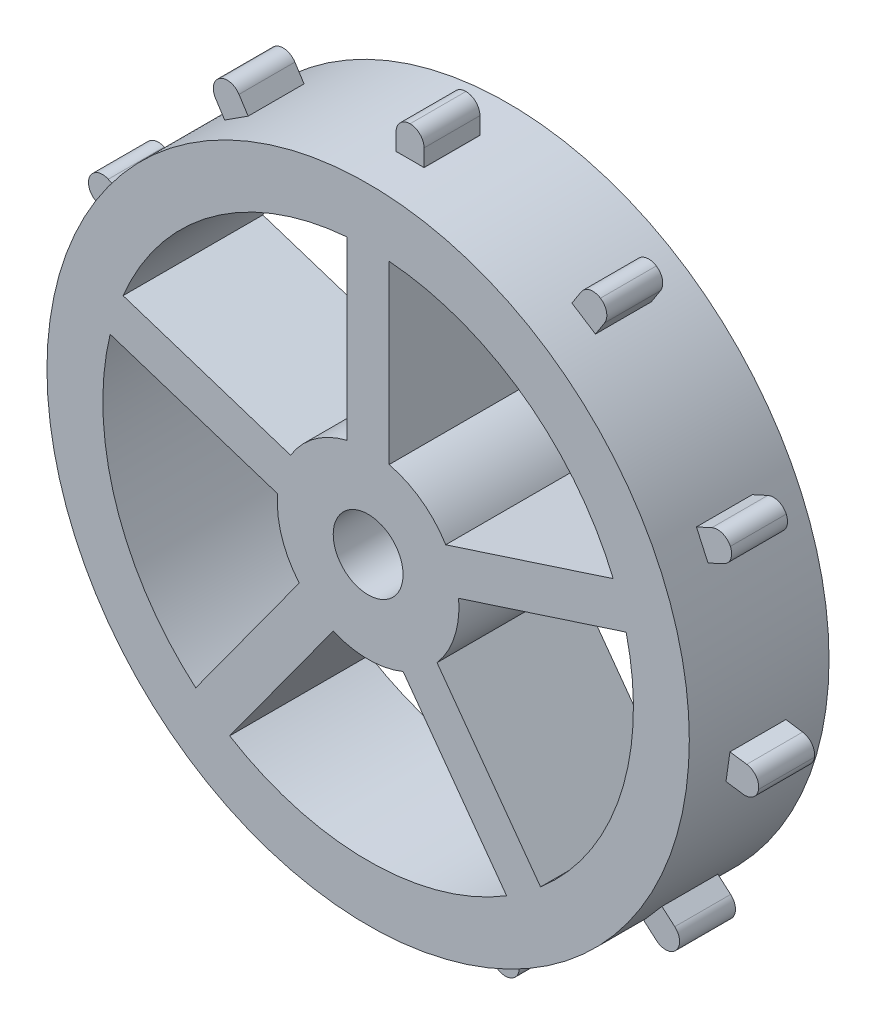
SolidWorks part; units mm, degrees
ref_plane "Front Plane" through (0, 0, 0) normal (0, 0, 1) x (1, 0, 0)
ref_plane "Top Plane" through (0, 0, 0) normal (0, 1, 0) x (1, 0, 0)
ref_plane "Right Plane" through (0, 0, 0) normal (1, 0, 0) x (0, 0, -1)
sketch "Sketch2" plane through (0, 0, 0) normal (0, 0, 1) x (1, 0, 0)
  line L0 (-6.75, 22.9884) -> (6.75, 22.9884)
  line L3 (6.75, 22.9884) -> (18.1069, 15.6897)
  line L4 (18.1069, 15.6897) -> (23.715, 3.4097)
  line L5 (23.715, 3.4097) -> (21.7938, -9.9529)
  line L6 (21.7938, -9.9529) -> (12.9532, -20.1555)
  line L7 (12.9532, -20.1555) -> (0, -23.9589)
  line L8 (0, -23.9589) -> (-12.9532, -20.1555)
  line L9 (-12.9532, -20.1555) -> (-21.7938, -9.9529)
  line L10 (-21.7938, -9.9529) -> (-23.715, 3.4097)
  line L11 (-23.715, 3.4097) -> (-18.1069, 15.6897)
  line L12 (-18.1069, 15.6897) -> (-6.75, 22.9884)
  line L13 (11.5754, 19.8614) -> (12.6567, 21.5439)
  line L14 (-1, 22.9666) -> (1, 22.9666)
  line L15 (-1, 22.9666) -> (-1, 24.9666)
  line L17 (1, 22.9666) -> (1, 24.9666)
  line L18 (13.258, 18.7801) -> (14.3392, 20.4626)
  line L19 (20.4758, 10.4503) -> (22.295, 11.2811)
  line L20 (21.3066, 8.6311) -> (23.1259, 9.4619)
  line L21 (22.8752, -2.2787) -> (24.8548, -2.5633)
  line L22 (22.5905, -4.2583) -> (24.5702, -4.5429)
  line L23 (18.0119, -14.2842) -> (19.5234, -15.5939)
  line L24 (16.7022, -15.7957) -> (18.2137, -17.1054)
  line L25 (7.4299, -21.7546) -> (7.9934, -23.6736)
  line L26 (5.511, -22.3181) -> (6.0744, -24.237)
  line L27 (-5.511, -22.3181) -> (-6.0744, -24.237)
  line L28 (-7.4299, -21.7546) -> (-7.9934, -23.6736)
  line L29 (-16.7022, -15.7957) -> (-18.2137, -17.1054)
  line L30 (-18.0119, -14.2842) -> (-19.5234, -15.5939)
  line L31 (-22.5905, -4.2583) -> (-24.5702, -4.5429)
  line L32 (-22.8752, -2.2787) -> (-24.8548, -2.5633)
  line L33 (-10.226, -55.112) -> (-10.7895, -57.031)
  line L34 (-21.3066, 8.6311) -> (-23.1259, 9.4619)
  line L35 (-20.4758, 10.4503) -> (-22.295, 11.2811)
  line L36 (-13.258, 18.7801) -> (-14.3392, 20.4626)
  line L37 (-30.6601, -41.9798) -> (-32.1716, -43.2896)
  line L38 (-11.5754, 19.8614) -> (-12.6567, 21.5439)
  line L47 (29.3503, -43.4913) -> (30.8618, -44.8011) [skipped]
  line L48 (30.6601, -41.9798) -> (32.1716, -43.2896) [skipped]
  line L49 (39.1561, -23.376) -> (41.1358, -23.6606) [skipped]
  line L50 (39.4408, -21.3964) -> (41.4204, -21.681) [skipped]
  line L51 (35.6993, 0.6667) -> (37.5186, 1.4976) [skipped]
  line L52 (36.5301, -1.1525) -> (38.3494, -0.3217) [skipped]
  line L53 (-29.3503, -43.4913) -> (-30.8618, -44.8011) [skipped]
  line L54 (-12.145, -54.5485) -> (-12.7085, -56.4675) [skipped]
  line L55 (12.145, -54.5485) -> (12.7085, -56.4675) [skipped]
  line L56 (10.226, -55.112) -> (10.7895, -57.031) [skipped]
  line L57 (20.6236, 17.2046) -> (21.7049, 18.8871) [skipped]
  line L58 (22.3061, 16.1233) -> (23.3874, 17.8059) [skipped]
  line L59 (-22.3061, 16.1233) -> (-23.3874, 17.8059) [skipped]
  line L60 (-20.6236, 17.2046) -> (-21.7049, 18.8871) [skipped]
  line L61 (-39.1561, -23.376) -> (-41.1358, -23.6606) [skipped]
  line L62 (-39.4408, -21.3964) -> (-41.4204, -21.681) [skipped]
  line L63 (-36.5301, -1.1525) -> (-38.3494, -0.3217) [skipped]
  line L64 (-35.6993, 0.6667) -> (-37.5186, 1.4976) [skipped]
  circle A0 centre (0, 0) radius 22.9884
  arc A1 (1, 24.9666) -> (-1, 24.9666) centre (0, 22.9666) ccw
  arc A2 (14.3392, 20.4626) -> (12.6567, 21.5439) centre (12.4167, 19.3208) ccw
  arc A3 (23.1259, 9.4619) -> (22.295, 11.2811) centre (20.8912, 9.5407) ccw
  arc A4 (24.5702, -4.5429) -> (24.8548, -2.5633) centre (22.7329, -3.2685) ccw
  arc A5 (18.2137, -17.1054) -> (19.5234, -15.5939) centre (17.357, -15.0399) ccw
  arc A6 (6.0744, -24.237) -> (7.9934, -23.6736) centre (6.4704, -22.0363) ccw
  arc A7 (-7.9934, -23.6736) -> (-6.0744, -24.237) centre (-6.4704, -22.0363) ccw
  arc A8 (-19.5234, -15.5939) -> (-18.2137, -17.1054) centre (-17.357, -15.0399) ccw
  arc A9 (-24.8548, -2.5633) -> (-24.5702, -4.5429) centre (-22.7329, -3.2685) ccw
  arc A10 (-22.295, 11.2811) -> (-23.1259, 9.4619) centre (-20.8912, 9.5407) ccw
  arc A11 (-12.6567, 21.5439) -> (-14.3392, 20.4626) centre (-12.4167, 19.3208) ccw
  point P4 (0, 22.9884)
  dimension "D1" = 13.5
  dimension "D2" = 6.75
  dimension "D4" = 1
  dimension "D5" = 2
  dimension "D6" = 2
  dimension "D3" = 11
  dimension "D7" = 11
  dimension "D8" = 11
extrude "Boss-Extrude1" add sketch "Sketch2" along normal blind 4 contours A0 L14 | L0 L17 L15 | L12 | L11 | L3 | L4 | L10 | L22 A4 L21 L5 | L24 A5 L23 L6 | L26 A6 L25 L7 | L28 A7 L27 L8 | L30 A8 L29 L9 region at (0, 24.0582, 0) region at (-13.0068, 20.2391, 0) region at (0, -0.0004, 0) region at (13.0068, 20.2391, 0) region at (-21.8841, 9.9941, 0) region at (21.8841, 9.9941, 0) region at (-23.8133, -3.4238, 0) region at (23.8133, -3.4238, 0) region at (-18.182, -15.7548, 0) region at (-6.778, -23.0837, 0) region at (18.182, -15.7548, 0) region at (6.778, -23.0837, 0)
sketch "Sketch5" plane through (0, 0, 4) normal (0, 0, 1) x (1, 0, 0)
  circle A0 centre (0, 0) radius 22.9884
extrude "Boss-Extrude3" add sketch "Sketch5" along normal blind 3
sketch "Sketch6" plane through (0, 0, 0) normal (0, 0, -1) x (-1, 0, 0)
  circle A0 centre (0, 0) radius 22.9884
extrude "Boss-Extrude4" add sketch "Sketch6" along normal blind 3
sketch "Sketch7" plane through (0, 0, -3) normal (0, 0, -1) x (-1, 0, 0)
  circle A0 centre (0, 0) radius 2.5
  dimension "D1" = 5
extrude "Cut-Extrude1" cut sketch "Sketch7" against normal blind 10
sketch "Sketch8" plane through (0, 0, -3) normal (0, 0, -1) x (-1, 0, 0)
  line L0 (0, 6.5) -> (0, 18.9884) construction
  line L1 (-1.5, 6.3246) -> (-1.5, 18.929)
  line L2 (1.5, 6.3246) -> (1.5, 18.929)
  line L3 (6.4785, 0.5278) -> (18.4661, 4.4228)
  line L4 (5.5515, 3.381) -> (17.5391, 7.276)
  line L5 (2.504, -5.9984) -> (9.9127, -16.1956)
  line L6 (4.931, -4.235) -> (12.3397, -14.4322)
  line L7 (-4.931, -4.235) -> (-12.3397, -14.4322)
  line L8 (-2.504, -5.9984) -> (-9.9127, -16.1956)
  line L9 (-5.5515, 3.381) -> (-17.5391, 7.276)
  line L10 (-6.4785, 0.5278) -> (-18.4661, 4.4228)
  circle A0 centre (0, 0) radius 6.5
  circle A1 centre (0, 0) radius 18.9884
  circle A2 centre (0, 0) radius 22.9884 construction
  circle A3 centre (0, 0) radius 2.5 construction
  dimension "D1" = 4
  dimension "D2" = 4
  dimension "D3" = 3
  dimension "D4" = 1.5
  dimension "D5" = 5
extrude "Cut-Extrude2" cut sketch "Sketch8" against normal blind 10 contours L1 A1 L9 A0 | L4 A1 L2 A0 | L6 A1 L3 A0 | L8 A1 L5 A0 | L10 A1 L7 A0 region at (7.8616, 10.8205, -3) region at (-7.8616, 10.8205, -3) region at (12.7203, -4.1331, -3) region at (-12.7203, -4.1331, -3) region at (0, -13.3749, -3)
fillet "Fillet1" radius 1 2 edges at (-1, 24.9666, 2) (1, 24.9666, 2)
fillet "Fillet2" radius 1 2 edges at (-14.3392, 20.4626, 2) (-12.6567, 21.5439, 2)
fillet "Fillet3" radius 1 2 edges at (-23.1259, 9.4619, 2) (-22.295, 11.2811, 2)
fillet "Fillet4" radius 1 2 edges at (-24.8548, -2.5633, 2) (-24.5702, -4.5429, 2)
fillet "Fillet5" radius 1 2 edges at (-18.2137, -17.1054, 2) (-19.5234, -15.5939, 2)
fillet "Fillet6" radius 1 2 edges at (-7.9934, -23.6736, 2) (-6.0744, -24.237, 2)
fillet "Fillet7" radius 1 2 edges at (7.9934, -23.6736, 2) (6.0744, -24.237, 2)
fillet "Fillet8" radius 1 2 edges at (14.3392, 20.4626, 2) (12.6567, 21.5439, 2)
fillet "Fillet9" radius 1 2 edges at (22.295, 11.2811, 2) (23.1259, 9.4619, 2)
fillet "Fillet10" radius 1 2 edges at (24.8548, -2.5633, 2) (24.5702, -4.5429, 2)
fillet "Fillet11" radius 1 2 edges at (18.2137, -17.1054, 2) (19.5234, -15.5939, 2)
